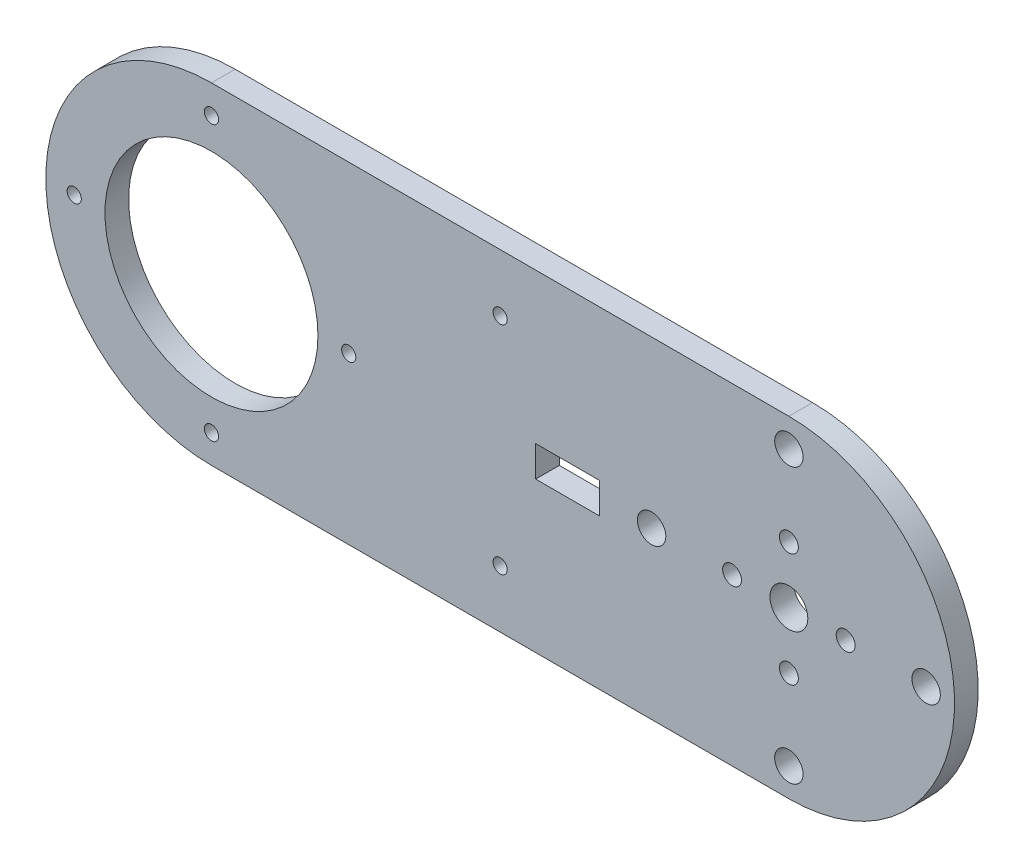
SolidWorks part; units mm, degrees
ref_plane "Front Plane" through (0, 0, 0) normal (0, 0, 1) x (1, 0, 0)
ref_plane "Top Plane" through (0, 0, 0) normal (0, 1, 0) x (1, 0, 0)
ref_plane "Right Plane" through (0, 0, 0) normal (1, 0, 0) x (0, 0, -1)
sketch "Sketch1" plane through (0, 0, 0) normal (0, 0, 1) x (1, 0, 0)
  line L0 (61, 0) -> (-61, 0) construction
  line L2 (61, -35) -> (-61, -35)
  line L3 (61, 35) -> (-61, 35)
  line L17 (7.5, 3.25) -> (7.5, -3.25)
  line L20 (7.5, -3.25) -> (21, -3.25)
  line L23 (21, -3.25) -> (21, 3.25)
  line L24 (21, 3.25) -> (7.5, 3.25)
  arc A0 (61, -35) -> (61, 35) centre (61, 0) ccw
  arc A1 (-61, 35) -> (-61, -35) centre (-61, 0) ccw
  circle A2 centre (61, 0) radius 4
  circle A3 centre (-61, 0) radius 22.5
  circle A4 centre (-61, -29) radius 1.5
  circle A5 centre (-61, 29) radius 1.5
  circle A6 centre (61, 29) radius 3
  circle A7 centre (61, -29) radius 3
  circle A8 centre (0, -22.8728) radius 1.5
  circle A9 centre (0, 22.8728) radius 1.5
  circle A12 centre (-90, 0) radius 1.5
  circle A13 centre (-32, 0) radius 1.5
  circle A16 centre (90, 0) radius 3
  circle A17 centre (32, 0) radius 3
  circle A34 centre (61, 12) radius 2
  circle A35 centre (61, -12) radius 2
  circle A36 centre (49, 0) radius 2
  circle A37 centre (73, 0) radius 2
  point P5 (0, 0)
  point P27 (-61, 0)
  point P28 (7.5, 0)
  point P32 (-61, 0)
  dimension "D1" = 8
  dimension "D3" = 6
  dimension "D4" = 3
  dimension "D5" = 6
  dimension "D6" = 3
  dimension "D8" = 6
  dimension "D9" = 6
  dimension "D12" = 3
  dimension "D13" = 3
  dimension "D14" = 70
  dimension "D15" = 12
  dimension "D16" = 12
  dimension "D19" = 3
  dimension "D20" = 3
  dimension "D24" = 29
  dimension "D25" = 6
  dimension "D26" = 6
  dimension "D27" = 4
  dimension "D28" = 4
  dimension "D29" = 4
  dimension "D30" = 29
  dimension "D31" = 13.5
  dimension "D32" = 6.5
  dimension "D33" = 68.5
  dimension "D45" = 45
  dimension "D22" = 4
  dimension "D7" = 122
  dimension "D10" = 6
  dimension "D11" = 6
  dimension "D17" = 12
  dimension "D18" = 58
  dimension "D21" = 12
  dimension "D23" = 29
extrude "Boss-Extrude1" add sketch "Sketch1" along normal blind 5
